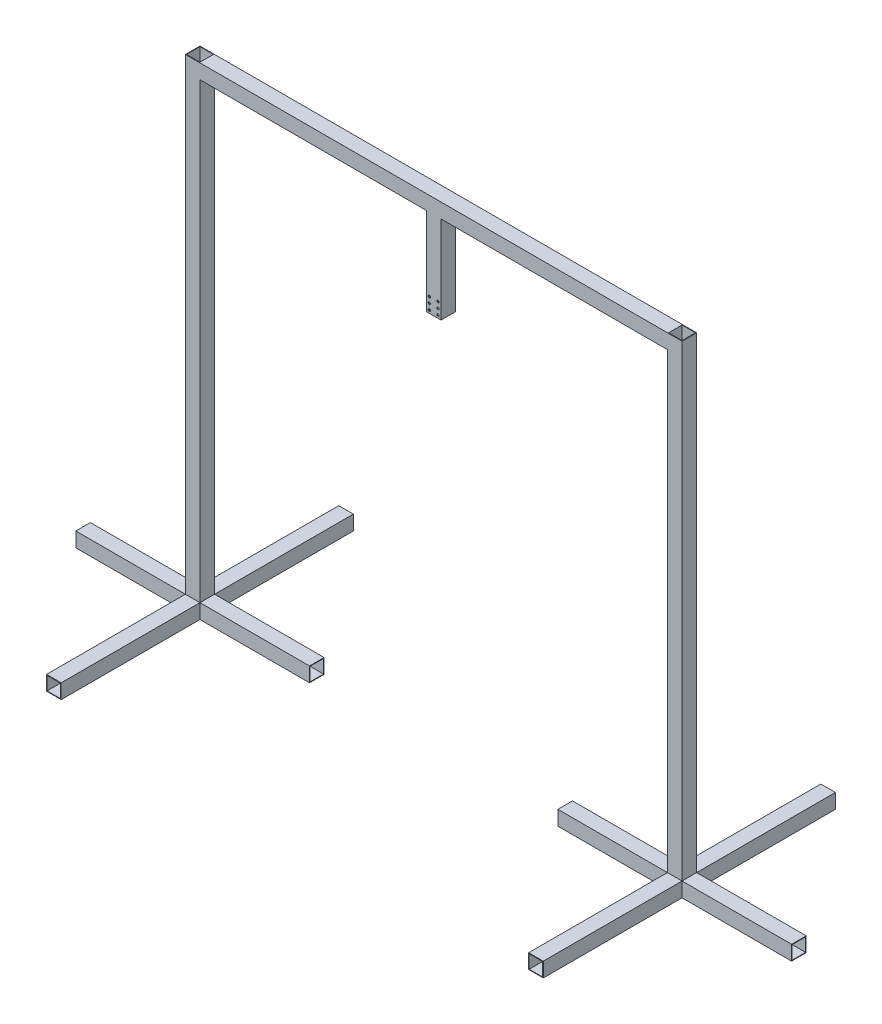
SolidWorks part; units mm, degrees
ref_plane "Front Plane" through (0, 0, 0) normal (0, 0, 1) x (1, 0, 0)
ref_plane "Top Plane" through (0, 0, 0) normal (0, 1, 0) x (1, 0, 0)
ref_plane "Right Plane" through (0, 0, 0) normal (1, 0, 0) x (0, 0, -1)
sketch "Sketch1" plane through (0, 0, 0) normal (0, 0, 1) x (1, 0, 0)
  line L1 (-12.5, 12.5) -> (12.5, 12.5)
  line L2 (-12.5, 12.5) -> (-12.5, -12.5)
  line L3 (-12.5, -12.5) -> (12.5, -12.5)
  line L4 (12.5, 12.5) -> (12.5, -12.5)
  line L7 (-11.5, 11.5) -> (11.5, 11.5)
  line L8 (-11.5, 11.5) -> (-11.5, -11.5)
  line L9 (-11.5, -11.5) -> (11.5, -11.5)
  line L10 (11.5, 11.5) -> (11.5, -11.5)
  point P0 (0, 0)
  point P6 (0, 0)
  dimension "D1" = 11.5
  dimension "D2" = 11.5
  dimension "D3" = 23
  dimension "D4" = 23
  dimension "D5" = 12.5
  dimension "D6" = 12.5
  dimension "D7" = 25
  dimension "D8" = 25
extrude "Boss-Extrude1" add sketch "Sketch1" along normal blind 250 and the other way blind 250
sketch "Sketch2" plane through (0, 0, 0) normal (1, 0, 0) x (0, 0, -1)
  line L0 (250, -12.5) -> (-250, -12.5) construction
  line L1 (-12.5, 12.5) -> (12.5, 12.5)
  line L2 (-12.5, 12.5) -> (-12.5, -12.5)
  line L3 (-12.5, -12.5) -> (12.5, -12.5)
  line L4 (12.5, 12.5) -> (12.5, -12.5)
  line L8 (-11.5, 11.5) -> (11.5, 11.5)
  line L9 (-11.5, 11.5) -> (-11.5, -11.5)
  line L10 (-11.5, -11.5) -> (11.5, -11.5)
  line L11 (11.5, 11.5) -> (11.5, -11.5)
  point P0 (0, 0)
  point P8 (0, 0)
  dimension "D1" = 11.5
  dimension "D2" = 12.5
  dimension "D3" = 11.5
  dimension "D4" = 12.5
  dimension "D5" = 11.5
  dimension "D6" = 12.5
  dimension "D7" = 11.5
extrude "Boss-Extrude2" add sketch "Sketch2" along normal blind 200 and the other way blind 200
sketch "Sketch3" plane through (0, 0, 0) normal (0, 1, 0) x (1, 0, 0)
  line L1 (-12.5, 12.5) -> (12.5, 12.5)
  line L2 (-12.5, 12.5) -> (-12.5, -12.5)
  line L3 (-12.5, -12.5) -> (12.5, -12.5)
  line L4 (12.5, 12.5) -> (12.5, -12.5)
  line L5 (-12.5, 12.5) -> (12.5, -12.5) construction
  line L6 (-12.5, -12.5) -> (12.5, 12.5) construction
  line L7 (-11.5, 11.5) -> (11.5, 11.5)
  line L8 (-11.5, 11.5) -> (-11.5, -11.5)
  line L9 (-11.5, -11.5) -> (11.5, -11.5)
  line L10 (11.5, 11.5) -> (11.5, -11.5)
  line L11 (-11.5, 11.5) -> (11.5, -11.5) construction
  line L12 (-11.5, -11.5) -> (11.5, 11.5) construction
  point P0 (0, 0)
  point P7 (0, 0)
sketch "Sketch4" plane through (0, -12.5, 0) normal (0, -1, 0) x (1, 0, 0)
  line L1 (-12.5, 12.5) -> (12.5, 12.5)
  line L2 (-12.5, 12.5) -> (-12.5, -12.5)
  line L3 (-12.5, -12.5) -> (12.5, -12.5)
  line L4 (12.5, 12.5) -> (12.5, -12.5)
  line L5 (-12.5, 12.5) -> (12.5, -12.5) construction
  line L6 (-12.5, -12.5) -> (12.5, 12.5) construction
  point P0 (0, 0)
extrude "Cut-Extrude6" cut sketch "Sketch4" against normal blind 25
extrude "Boss-Extrude3" add sketch "Sketch3" along normal blind 825 from offset 12.5 offset against normal yes
sketch "Sketch5" plane through (-12.5, 0, 0) normal (-1, 0, 0) x (0, 0, 1)
  line L0 (12.5, 812.5) -> (12.5, 12.5) construction
  line L1 (-12.5, 812.5) -> (12.5, 812.5)
  line L2 (-12.5, 812.5) -> (-12.5, 787.5)
  line L3 (-12.5, 787.5) -> (12.5, 787.5)
  line L4 (12.5, 812.5) -> (12.5, 787.5)
  line L5 (-12.5, 812.5) -> (12.5, 787.5) construction
  line L6 (-12.5, 787.5) -> (12.5, 812.5) construction
  line L7 (-12.5, 812.5) -> (12.5, 812.5) construction
  line L8 (-11.5, 788.5) -> (11.5, 788.5)
  line L9 (11.5, 811.5) -> (11.5, 788.5)
  line L10 (-11.5, 811.5) -> (11.5, 811.5)
  line L11 (-11.5, 811.5) -> (-11.5, 788.5)
  point P0 (0, 800)
  dimension "D1" = 0
  dimension "D3" = 25
  dimension "D4" = 25
  dimension "D2" = 1
extrude "Boss-Extrude4" add sketch "Sketch5" along normal blind 400
mirror "Mirror1" about plane through (-412.5, 0, 0) normal (-1, 0, 0) of "Boss-Extrude3", "Cut-Extrude6", "Boss-Extrude1", "Boss-Extrude2", "Boss-Extrude4"
sketch "Sketch6" plane through (0, 787.5, 0) normal (0, -1, 0) x (1, 0, 0)
  line L0 (-812.5, -12.5) -> (-12.5, -12.5) construction
  line L1 (-425, 12.5) -> (-400, 12.5)
  line L2 (-425, 12.5) -> (-425, -12.5)
  line L3 (-425, -12.5) -> (-400, -12.5)
  line L4 (-400, 12.5) -> (-400, -12.5)
  line L5 (-425, 12.5) -> (-400, -12.5) construction
  line L6 (-425, -12.5) -> (-400, 12.5) construction
  line L7 (-812.5, -12.5) -> (-812.5, 12.5) construction
  line L8 (-424, 11.5) -> (-401, 11.5)
  line L9 (-424, 11.5) -> (-424, -11.5)
  line L10 (-424, -11.5) -> (-401, -11.5)
  line L11 (-401, 11.5) -> (-401, -11.5)
  line L12 (-424, 11.5) -> (-401, -11.5) construction
  line L13 (-424, -11.5) -> (-401, 11.5) construction
  point P0 (-412.5, 0)
  point P7 (-412.5, 0)
  dimension "D1" = 400
extrude "Boss-Extrude5" add sketch "Sketch6" along normal blind 150
sketch "Sketch7" plane through (0, 0, 12.5) normal (0, 0, 1) x (1, 0, 0)
  line L0 (-400, 637.5) -> (-425, 637.5) construction
  line L1 (-400, 637.5) -> (-400, 787.5) construction
  circle A0 centre (-420, 662.5) radius 2
  circle A1 centre (-405, 662.5) radius 2
  circle A2 centre (-420, 652.5) radius 2
  circle A3 centre (-405, 652.5) radius 2
  circle A4 centre (-420, 642.5) radius 2
  circle A5 centre (-405, 642.5) radius 2
  dimension "D1" = 15
  dimension "D2" = 15
  dimension "D3" = 15
  dimension "D4" = 5
  dimension "D5" = 5
  dimension "D6" = 10
  dimension "D7" = 10
  dimension "D8" = 10
  dimension "D9" = 10
  dimension "D10" = 5
  dimension "D11" = 5
  dimension "D12" = 5
extrude "Cut-Extrude7" cut sketch "Sketch7" against normal blind 25
